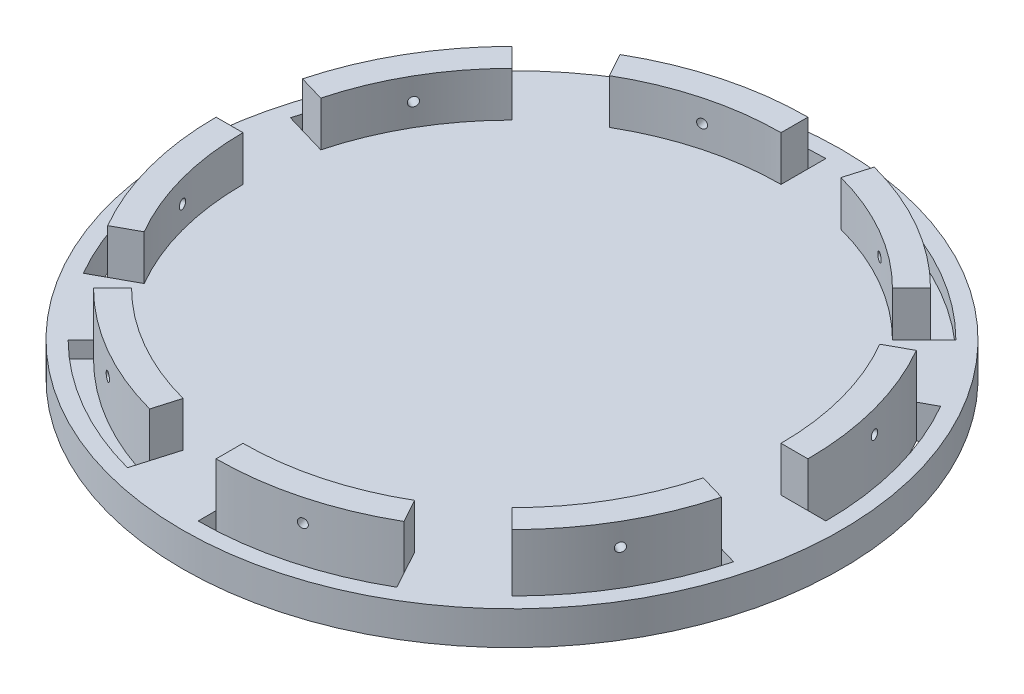
SolidWorks part; units mm, degrees
material "6061-T6 (SS)"
ref_plane "Front Plane" through (0, 0, 0) normal (0, 0, 1) x (1, 0, 0)
ref_plane "Top Plane" through (0, 0, 0) normal (0, 1, 0) x (1, 0, 0)
ref_plane "Right Plane" through (0, 0, 0) normal (1, 0, 0) x (0, 0, -1)
sketch "Sketch1" plane through (0, 0, 0) normal (0, 1, 0) x (1, 0, 0)
  circle A0 centre (0, 0) radius 93.345
  dimension "D1" = 186.69
extrude "Base" add sketch "Sketch1" along normal blind 4.7625 and the other way blind 4.7625
sketch "Sketch2" plane through (0, 4.7625, 0) normal (0, 1, 0) x (1, 0, 0)
  line L0 (0, 0) -> (0, 93.345) construction
  line L1 (-55, 0) -> (55, 0) construction
  line L2 (0, 88.9) -> (0, 83.82)
  line L3 (-41.9567, 72.5633) -> (-44.3929, 77.0226)
  line L4 (0, 0) -> (0, 93.345) construction
  arc A0 (-41.9567, 72.5633) -> (0, 83.82) centre (0, 0) cw
  arc A1 (-44.3929, 77.0226) -> (0, 88.9) centre (0, 0) cw
  circle A8 centre (0, 0) radius 93.345 construction
  dimension "D1" = 83.82
  dimension "D3" = 43.942
  dimension "D4" = 46.482
  dimension "D2" = 88.9
extrude "Bottom support holes" cut sketch "Sketch2" against normal through all
sketch "Sketch3" plane through (0, 4.7625, 0) normal (0, 1, 0) x (1, 0, 0)
  line L0 (0, 0) -> (0, 93.345) construction
  line L2 (0, 83.82) -> (0, 76.2)
  line L3 (-38.3023, 65.8739) -> (-41.9567, 72.5633)
  line L4 (-55, 0) -> (55, 0) construction
  line L7 (-44.3929, 77.0226) -> (-41.9567, 72.5633) construction
  arc A0 (-38.3023, 65.8739) -> (0, 76.2) centre (0, 0) cw
  arc A1 (-41.9567, 72.5633) -> (0, 83.82) centre (0, 0) cw
  circle A2 centre (0, 0) radius 93.345 construction
  dimension "D1" = 76.2
  dimension "D4" = 43.942
  dimension "D2" = 83.82
extrude "Bottom support guide" add sketch "Sketch3" along normal blind 12.7
ref_plane "Bottom bolt hole plane" through (-20.9784, 0, -78.1916) normal (-0.2591, 0, -0.9658) x (-0.9658, 0, 0.2591)
sketch "Sketch6" plane through (-20.9784, 0, -78.1916) normal (-0.2591, 0, -0.9658) x (-0.9658, 0, 0.2591)
  line L0 (22.9177, 4.7625) -> (-23.0366, 4.7625) construction
  line L1 (-21.7203, 4.7625) -> (-21.7203, 17.4625) construction
  circle A0 centre (-0.0033, 11.1125) radius 1.27
  dimension "D1" = 2.54
  dimension "D2" = 6.35
  dimension "D3" = 21.717
extrude "Bottom bolt hole" cut sketch "Sketch6" against normal blind 12.7 and the other way blind 12.7
sketch "Sketch8" plane through (-31.123, 4.7625, 77.2967) normal (0, 1, 0) x (1, 0, 0)
  line L0 (31.123, 77.2967) -> (-34.8819, 143.3016) construction
  line L2 (-31.7388, 140.1585) -> (-28.1467, 136.5664)
  line L3 (-49.8549, 98.9388) -> (-54.7307, 100.3694)
  line L4 (31.123, 77.2967) -> (-34.8819, 143.3016) construction
  line L5 (31.123, 77.2967) -> (31.123, 170.6417) construction
  arc A0 (-49.8549, 98.9388) -> (-28.1467, 136.5664) centre (31.123, 77.2967) cw
  arc A1 (-54.7307, 100.3694) -> (-31.7388, 140.1585) centre (31.123, 77.2967) cw
  circle A3 centre (31.123, 77.2967) radius 93.345 construction
  dimension "D1" = 83.82
  dimension "D3" = 43.942
  dimension "D4" = 46.482
  dimension "D2" = 88.9
  dimension "D5" = 45
extrude "Top support holes" cut sketch "Sketch8" against normal blind 4.7625
sketch "Sketch10" plane through (-31.123, 4.7625, 77.2967) normal (0, 1, 0) x (1, 0, 0)
  line L0 (31.123, 77.2967) -> (-34.8819, 143.3016) construction
  line L2 (-28.1467, 136.5664) -> (-22.7586, 131.1782)
  line L3 (-42.5407, 96.7928) -> (-49.8549, 98.9388)
  line L7 (-54.7307, 100.3694) -> (-49.8549, 98.9388) construction
  arc A0 (-42.5407, 96.7928) -> (-22.7586, 131.1782) centre (31.123, 77.2967) cw
  arc A1 (-49.8549, 98.9388) -> (-28.1467, 136.5664) centre (31.123, 77.2967) cw
  dimension "D1" = 76.2
  dimension "D4" = 43.942
  dimension "D2" = 83.82
extrude "Top support guide" add sketch "Sketch10" along normal blind 12.7
ref_plane "Top bolt hole plane" through (-70.1238, 0, -40.4559) normal (-0.8662, 0, -0.4997) x (-0.4997, 0, 0.8662)
sketch "Sketch12" plane through (-70.1238, 0, -40.4559) normal (-0.8662, 0, -0.4997) x (-0.4997, 0, 0.8662)
  line L0 (22.9177, 4.7625) -> (-23.0366, 4.7625) construction
  line L1 (-21.7203, 4.7625) -> (-21.7203, 17.4625) construction
  circle A0 centre (-0.0033, 11.1125) radius 1.27
  dimension "D1" = 2.54
  dimension "D2" = 6.35
  dimension "D3" = 21.717
extrude "Top bolt hole" cut sketch "Sketch12" against normal blind 12.7 and the other way blind 12.7
pattern_circular "Bottom pattern" count 4 over 360 about axis through (0, 4.7625, 0) along (0, 1, 0) of "Bottom support holes", "Bottom support guide", "Bottom bolt hole"
pattern_circular "CirPattern3" count 4 over 360 about axis through (0, 4.7625, 0) along (0, 1, 0) of "Top support holes", "Top bolt hole", "Top support guide"
